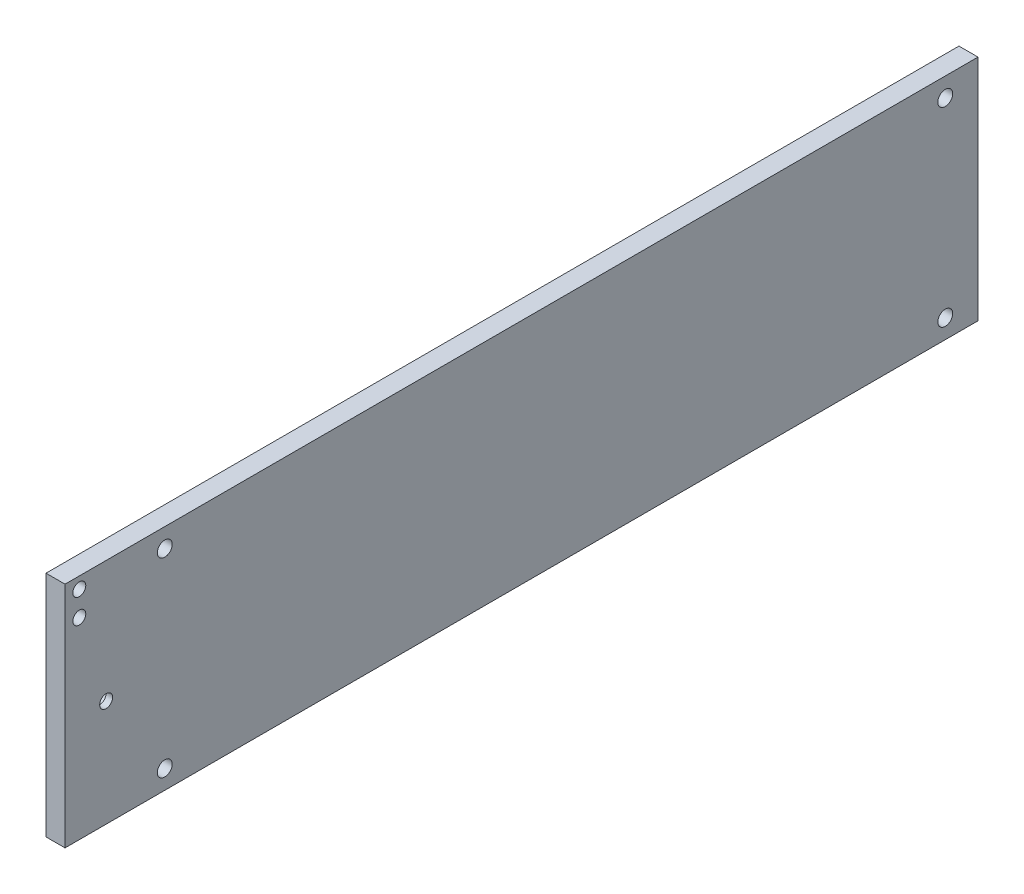
SolidWorks part; units mm, degrees
material "6061-T6 (SS)"
ref_plane "Front Plane" through (0, 0, 0) normal (0, 0, 1) x (1, 0, 0)
ref_plane "Top Plane" through (0, 0, 0) normal (0, 1, 0) x (1, 0, 0)
ref_plane "Right Plane" through (0, 0, 0) normal (1, 0, 0) x (0, 0, -1)
sketch "Sketch1" plane through (0, 0, 0) normal (1, 0, 0) x (0, 0, -1)
  line L1 (-152.273, 38.1) -> (152.273, 38.1)
  line L2 (-152.273, 38.1) -> (-152.273, -38.1)
  line L3 (-152.273, -38.1) -> (152.273, -38.1)
  line L4 (152.273, 38.1) -> (152.273, -38.1)
  line L5 (-152.273, 38.1) -> (152.273, -38.1) construction
  line L6 (-152.273, -38.1) -> (152.273, 38.1) construction
  point P0 (0, 0)
  dimension "D1" = 76.2
  dimension "D2" = 304.546
extrude "Boss-Extrude1" add sketch "Sketch1" along normal blind 6.35
sketch "Sketch2" plane through (6.35, 0, 0) normal (1, 0, 0) x (0, 0, -1)
  line L0 (152.273, -38.1) -> (152.273, 38.1) construction
  line L1 (-118.999, 31.75) -> (141.351, 31.75) construction
  line L2 (-118.999, 31.75) -> (-118.999, -31.75) construction
  line L3 (-118.999, -31.75) -> (141.351, -31.75) construction
  line L4 (141.351, 31.75) -> (141.351, -31.75) construction
  line L5 (-118.999, 31.75) -> (141.351, -31.75) construction
  line L6 (-118.999, -31.75) -> (141.351, 31.75) construction
  line L7 (-152.273, 38.1) -> (-152.273, -38.1) construction
  line L8 (-152.273, -38.1) -> (152.273, -38.1) construction
  point P0 (11.176, 0)
  point P7 (0, 0)
  point P8 (-138.557, -2.54)
  point P14 (0, 0)
  dimension "D1" = 10.922
  dimension "D2" = 33.274
  dimension "D3" = 63.5
  dimension "D4" = 13.716
  dimension "D5" = 35.56
hole_wizard "#10 Clearance Hole1" positions "Sketch3" profile "Sketch4" hole size "#10" standard "ANSI Inch" end condition through all
sketch "Sketch3" plane through (6.35, 0, 0) normal (1, 0, 0) x (0, 0, -1)
  point P0 (-118.999, 31.75)
  point P3 (-118.999, -31.75)
  point P6 (141.351, -31.75)
  point P9 (141.351, 31.75)
sketch "Sketch4" plane through (6.35, 31.75, 118.999) normal (0, 1, 0) x (0, 0, -1)
  line L0 (0, 0) -> (0, 6.35)
  line L1 (0, 6.35) -> (2.4892, 6.35)
  line L2 (2.4892, 6.35) -> (2.4892, 0)
  line L5 (2.4892, 0) -> (0, 0)
  line L11 (0, -6.35) -> (0, 107.95) construction
  dimension "Thru Hole Dia." = 4.9784
  dimension "Thru Hole Depth" = 6.35
hole_wizard "CBORE for #8 Socket Head Cap Screw2" positions "Sketch8" profile "Sketch9" counterbore size "#8" standard "ANSI Inch"
sketch "Sketch8" plane through (0, 0, 0) normal (-1, 0, 0) x (0, 0, 1)
  point P0 (138.557, -2.54)
  point P1 (0, 0)
  point P2 (135.208, -9.4942)
sketch "Sketch9" plane through (0, -2.54, 138.557) normal (0, 1, 0) x (0, 0, 1)
  line L0 (0, 0) -> (0, 11.9614)
  line L1 (0, 11.9614) -> (2.1526, 10.668)
  line L2 (2.1526, 10.668) -> (2.1526, 4.1656)
  line L3 (2.1526, 4.1656) -> (3.9687, 4.1656)
  line L4 (3.9687, 4.1656) -> (3.9687, 0)
  line L5 (3.9687, 0) -> (0, 0)
  line L10 (0, 11.9614) -> (-2.1527, 10.668) construction
  line L11 (0, -6.35) -> (0, 107.95) construction
  dimension "Hole Dia." = 4.3053
  dimension "Hole Depth" = 10.668
  dimension "C'Bore Dia." = 7.9375
  dimension "C'Bore Depth" = 4.1656
  dimension "Drill Angle" = 118
sketch "Sketch10" plane through (0, 0, 0) normal (-1, 0, 0) x (0, 0, 1)
  line L0 (147.5105, 34.2519) -> (147.5105, 26.0731) construction
  line L1 (152.273, 38.1) -> (152.273, -38.1) construction
  line L2 (-152.273, 38.1) -> (152.273, 38.1) construction
  point P2 (147.5105, 30.1625)
  dimension "D1" = 4.7625
  dimension "D2" = 7.9375
  dimension "D3" = 8.1788
hole_wizard "#8 Clearance Hole1" positions "Sketch11" profile "Sketch12" hole size "#8" standard "ANSI Inch" end condition through all
sketch "Sketch11" plane through (0, 0, 0) normal (-1, 0, 0) x (0, 0, 1)
  point P0 (147.5105, 34.2519)
  point P3 (147.5105, 26.0731)
sketch "Sketch12" plane through (0, 34.2519, 147.5105) normal (0, 1, 0) x (0, 0, 1)
  line L0 (0, 0) -> (0, 6.35)
  line L1 (0, 6.35) -> (2.1526, 6.35)
  line L2 (2.1526, 6.35) -> (2.1526, 0)
  line L5 (2.1526, 0) -> (0, 0)
  line L11 (0, -6.35) -> (0, 107.95) construction
  dimension "Thru Hole Dia." = 4.3053
  dimension "Thru Hole Depth" = 6.35
